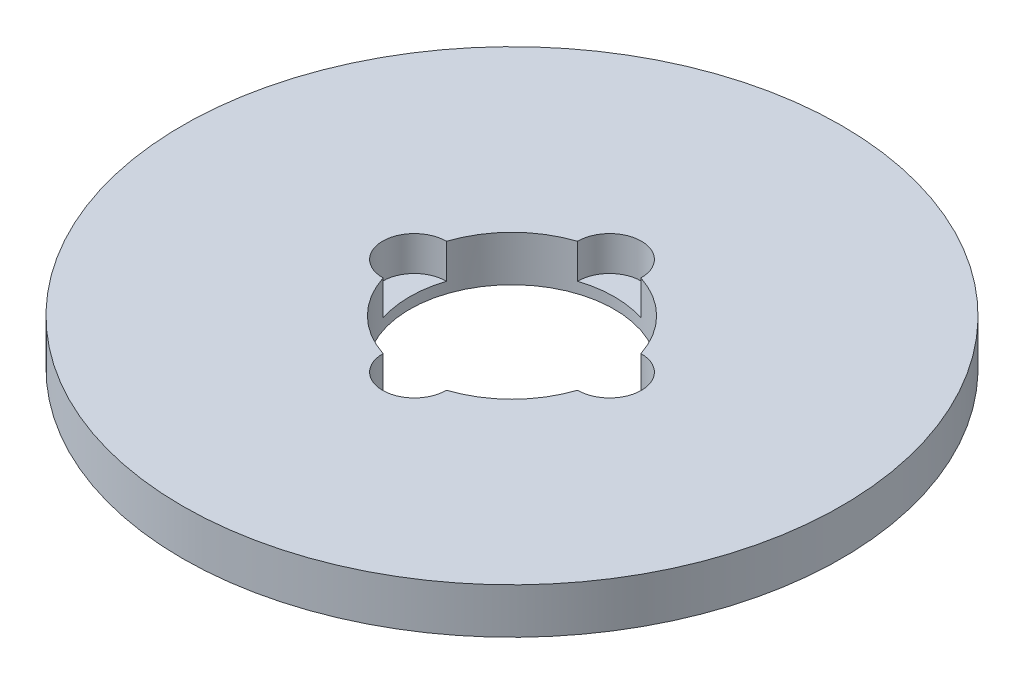
SolidWorks part; units mm, degrees
ref_plane "Front Plane" through (0, 0, 0) normal (0, 0, 1) x (1, 0, 0)
ref_plane "Top Plane" through (0, 0, 0) normal (0, 1, 0) x (1, 0, 0)
ref_plane "Right Plane" through (0, 0, 0) normal (1, 0, 0) x (0, 0, -1)
sketch "Sketch1" plane through (0, 0, 0) normal (0, 1, 0) x (1, 0, 0)
  circle A0 centre (0, 0) radius 72.5
  dimension "FLANGE_OD" = 145
extrude "Boss-Extrude1" add sketch "Sketch1" along normal blind 10
sketch "Sketch2" plane through (0, 0, 0) normal (0, 1, 0) x (1, 0, 0)
  circle A0 centre (0, 0) radius 22.5
  dimension "BORE_D" = 45
extrude "Cut-Extrude1" cut sketch "Sketch2" along normal through all
sketch "Sketch3" plane through (0, 10, 0) normal (0, 1, 0) x (1, 0, 0)
  circle A0 centre (0, 0) radius 21.4751 construction
  circle A1 centre (-21.4751, 0) radius 6.9705
  dimension "BOLT_D" = 13.941
  dimension "BOLT_PCD" = 42.9502
extrude "Cut-Extrude2" cut sketch "Sketch3" against normal blind 7.6117
pattern_circular "CirPattern1" count 4 over 360 about axis through (0, 0, 0) along (0, 1, 0) of "Cut-Extrude2"
